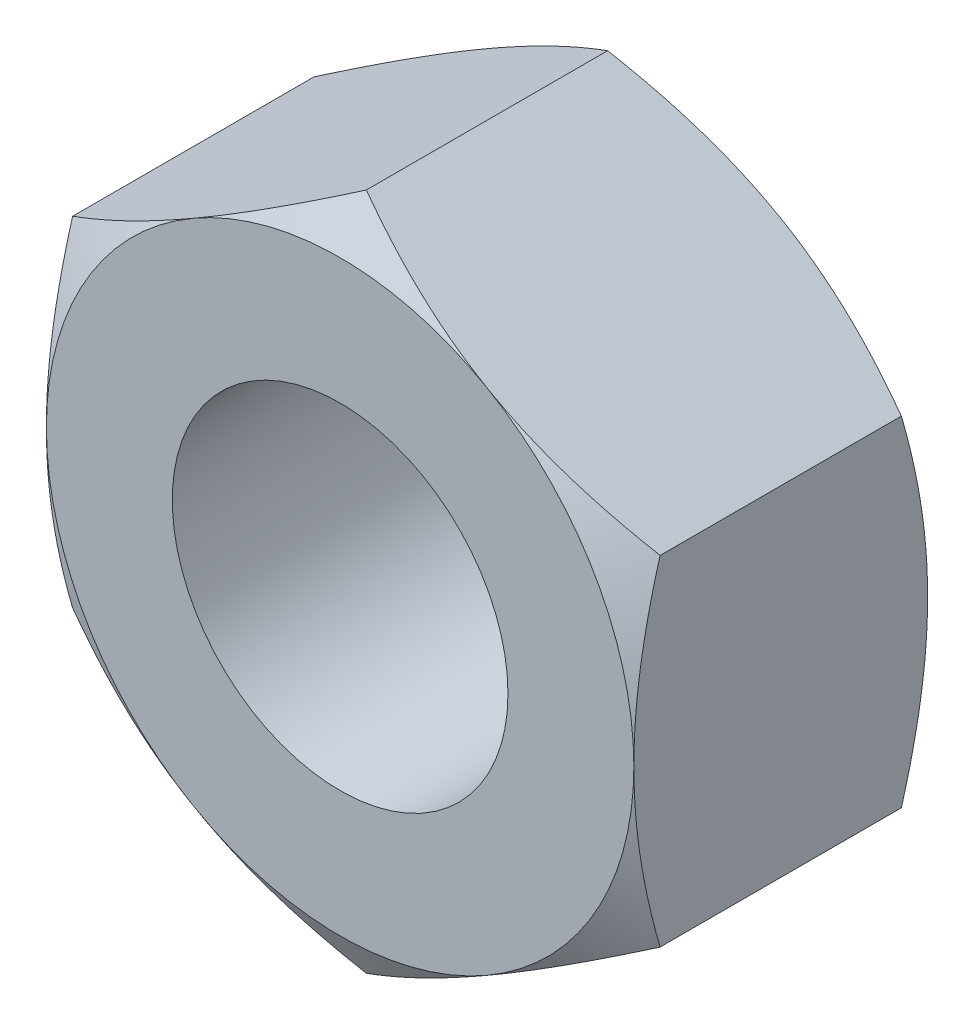
SolidWorks part; units mm, degrees
material "AISI 304"
ref_plane "Front" through (0, 0, 0) normal (0, 0, 1) x (1, 0, 0)
ref_plane "Top" through (0, 0, 0) normal (0, 1, 0) x (1, 0, 0)
ref_plane "Right" through (0, 0, 0) normal (1, 0, 0) x (0, 0, -1)
sketch "Sketch1" plane through (0, 0, 0) normal (0, 0, 1) x (1, 0, 0)
  line L1 (-5.5562, 3.2079) -> (-5.5562, -3.2079)
  line L2 (-5.5562, -3.2079) -> (0, -6.4158)
  line L3 (0, -6.4158) -> (5.5562, -3.2079)
  line L4 (5.5562, -3.2079) -> (5.5562, 3.2079)
  line L5 (5.5562, 3.2079) -> (0, 6.4158)
  line L6 (0, 6.4158) -> (-5.5562, 3.2079)
  circle A0 centre (0, 0) radius 5.5562 construction
  circle A1 centre (0, 0) radius 3.175
  point P10 (0, 3.175)
  dimension "hex" = 11.1125
  dimension "dia" = 6.35
extrude "Extrude1" add sketch "Sketch1" along normal mid plane 5.5562
sketch "Sketch4" plane through (0, 0, -2.7781) normal (0, 0, -1) x (-1, 0, 0)
  circle A0 centre (0, 0) radius 3.175 construction
  circle A1 centre (0, 0) radius 3.175
curve "Helix/Spiral3" pitch 1.27 height 6.6675 turns 5.25
sketch "Sketch3" plane through (0, 0, 0) normal (1, 0, 0) x (0, 0, -1)
  line L0 (2.7781, 3.175) -> (3.8894, 3.175)
  line L1 (3.8894, 3.175) -> (3.4131, 2.3501)
  line L2 (3.4131, 2.3501) -> (3.2544, 2.3501)
  line L3 (3.2544, 2.3501) -> (2.7781, 3.175)
  line L4 (3.0163, 2.7626) -> (3.6513, 2.7626) construction
  dimension "D1" = 60
  dimension "D2" = 0.635
  dimension "D3" = 0.1588
sweep "Sweep1" [suppressed] add profiles "Sketch3" path "Helix/Spiral3"
sketch "Sketch6" [suppressed] plane through (0, 0, 0) normal (1, 0, 0) x (0, 0, -1)
  line L0 (-3.0956, 3.4925) -> (-2.4606, 2.8575)
  line L1 (-2.4606, 2.8575) -> (-2.4606, 0) construction
  line L2 (3.0559, 0) -> (-3.0559, 0) construction
  line L3 (-2.4606, 0) -> (-3.8894, 0)
  line L4 (-3.8894, 0) -> (-3.8894, 3.4925)
  line L5 (-3.8894, 3.4925) -> (-3.0956, 3.4925)
  line L6 (-2.4606, 2.8575) -> (0.3969, 0)
  line L7 (0.3969, 0) -> (-2.4606, 0)
  line L8 (-2.7781, -3.2079) -> (-2.7781, 3.2079) construction
  point P2 (-2.7781, 3.175)
  dimension "D2" = 0.635
  dimension "D1" = 45
revolve "Cut-Revolve1" [suppressed] cut sketch "Sketch6" angle 360 about L3
sketch "Sketch7" plane through (0, 0, 2.7781) normal (0, 0, 1) x (1, 0, 0)
  circle A0 centre (0, 0) radius 5.5562 construction
  circle A1 centre (0, 0) radius 5.5562
extrude "Extrude2" cut sketch "Sketch7" against normal blind 25.4 draft 60 flip side to cut
mirror "Mirror1" about plane through (0, 0, 0) normal (0, 0, 1) of "Extrude2", "Cut-Revolve1"
sketch "Sketch8" [suppressed] plane through (0, 0, 2.7781) normal (0, 0, 1) x (1, 0, 0)
  line L0 (-2.2451, 2.2451) -> (0, 0) construction
  line L1 (0, -4.2816) -> (0, 4.2816) construction
  circle A0 centre (0, 0) radius 3.175 construction
  point P0 (-2.2451, 2.2451)
  dimension "D1" = 45
equation "\"D3@Helix/Spiral3\" = \"length@Extrude1\" * 1.2"
equation "\"D2@Sketch3\" = \"D4@Helix/Spiral3\" * .5"
equation "\"D3@Sketch3\" = \"D4@Helix/Spiral3\" * .125"
equation "\"D2@Sketch6\" = \"D4@Helix/Spiral3\" * .5"
